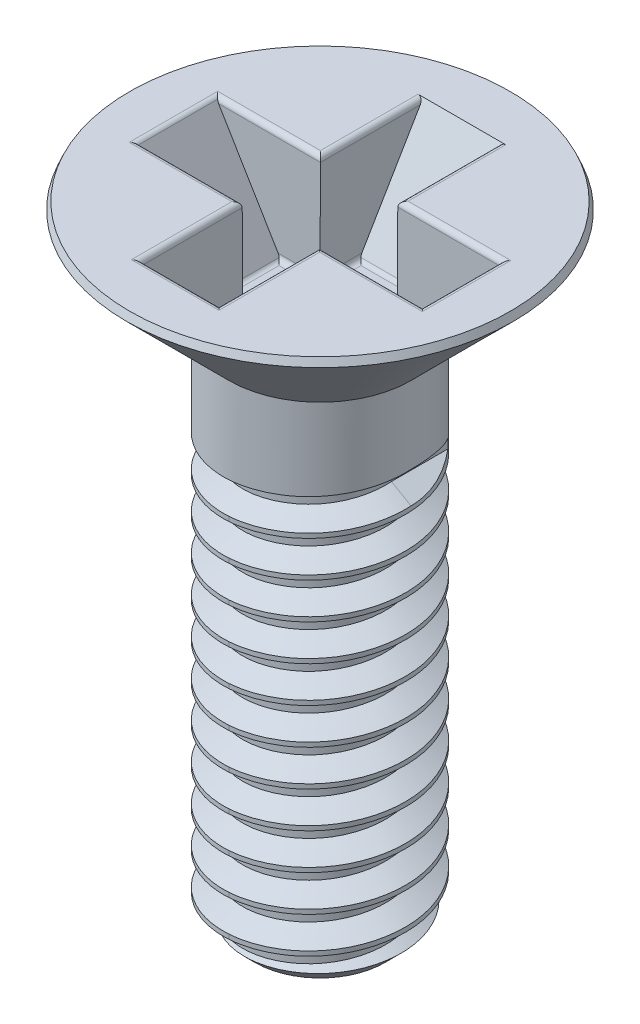
SolidWorks part; units mm, degrees
ref_plane "Alzado" through (0, 0, 0) normal (0, 0, 1) x (1, 0, 0)
ref_plane "Planta" through (0, 0, 0) normal (0, 1, 0) x (1, 0, 0)
ref_plane "Vista lateral" through (0, 0, 0) normal (1, 0, 0) x (0, 0, -1)
sketch "Croquis1" plane through (0, 0, 0) normal (0, 0, 1) x (1, 0, 0)
  line L0 (0, 0) -> (0, 5.3729) construction
  line L1 (0, 5.3729) -> (0, -5.1766) construction
  line L2 (0, 2.6864) -> (-3.6823, 2.6864)
  line L3 (-3.7409, 2.545) -> (-1.761, 0.5651)
  line L4 (-1.761, -8.9349) -> (-1.761, 0.5651)
  line L5 (-1.261, -9.4349) -> (0, -9.4349)
  line L6 (0, -9.4349) -> (0, 0.3991)
  line L9 (-1.261, -9.4349) -> (-1.761, -8.9349)
  line L10 (-3.6823, 2.6864) -> (-3.7409, 2.545)
  line L11 (0, 2.6864) -> (0, 0.3991)
  point P5 (-3.8823, 2.6864)
  point P7 (-1.761, -9.4349)
  dimension "D1" = 3
  dimension "D2" = 10
  dimension "D3" = 3.8823
  dimension "D4" = 45
  dimension "D5" = 1.761
revolve "Revolución1" add sketch "Croquis1" angle 360 about L11
ref_plane "Plano1" through (0, 0.5651, 0) normal (0, -1, 0) x (-1, 0, 0)
sketch "Croquis2" plane through (0, 0.5651, 0) normal (0, -1, 0) x (-1, 0, 0)
  line L0 (-0.75, 0.75) -> (-1.5, 0.75)
  line L1 (1.5, -0.75) -> (0.75, -0.75)
  line L2 (1.5, -0.75) -> (1.5, 0.75)
  line L3 (1.5, 0.75) -> (0.75, 0.75)
  line L4 (-1.5, -0.75) -> (-1.5, 0.75)
  line L5 (1.5, -0.75) -> (-1.5, 0.75) construction
  line L6 (1.5, 0.75) -> (-1.5, -0.75) construction
  line L7 (0.75, -1.5) -> (-0.75, -1.5)
  line L8 (0.75, -1.5) -> (0.75, -0.75)
  line L9 (0.75, 1.5) -> (-0.75, 1.5)
  line L10 (-0.75, -1.5) -> (-0.75, -0.75)
  line L11 (0.75, -1.5) -> (-0.75, 1.5) construction
  line L12 (0.75, 1.5) -> (-0.75, -1.5) construction
  line L13 (-0.75, 0.75) -> (-0.75, 1.5)
  line L14 (-0.75, -0.75) -> (-1.5, -0.75)
  line L15 (0.75, 0.75) -> (0.75, 1.5)
  point P0 (0, 0)
  point P6 (0, 0)
ref_plane "Plano3" through (0, 2.6864, 0) normal (0, 1, 0) x (1, 0, 0)
sketch "Croquis4" plane through (0, 2.6864, 0) normal (0, 1, 0) x (1, 0, 0)
  line L0 (0.7477, 0.7569) -> (0.7477, 2.7456)
  line L1 (-2.7792, -0.7569) -> (-0.7477, -0.7569)
  line L2 (-2.7792, -0.7569) -> (-2.7792, 0.7569)
  line L3 (-2.7792, 0.7569) -> (-0.7477, 0.7569)
  line L4 (2.7792, -0.7569) -> (2.7792, 0.7569)
  line L5 (-2.7792, -0.7569) -> (2.7792, 0.7569) construction
  line L6 (-2.7792, 0.7569) -> (2.7792, -0.7569) construction
  line L7 (-0.7477, -2.7456) -> (0.7477, -2.7456)
  line L8 (-0.7477, -2.7456) -> (-0.7477, -0.7569)
  line L9 (-0.7477, 2.7456) -> (0.7477, 2.7456)
  line L10 (0.7477, -2.7456) -> (0.7477, -0.7569)
  line L11 (-0.7477, -2.7456) -> (0.7477, 2.7456) construction
  line L12 (-0.7477, 2.7456) -> (0.7477, -2.7456) construction
  line L13 (0.7477, 0.7569) -> (2.7792, 0.7569)
  line L14 (-0.7477, 0.7569) -> (-0.7477, 2.7456)
  line L15 (0.7477, -0.7569) -> (2.7792, -0.7569)
  point P0 (0, 0)
  point P6 (0, 0)
loft "Cortar-Recubrir2" cut profiles "Croquis4", "Croquis2" connector at (-0.7477, 2.6864, 2.7456) connector at (-0.75, 0.5651, 1.5)
fillet "Redondeo1" radius 0.1 23 edges
thread "Rosca1" pitch 0.7 method cut profile "Perfil de rosca1" start angle 0, offset 1, length 0, pitch 0.7, diameter 3.522
ref_plane "Plano4" through (1.761, -9.9349, 0) normal (0, 0, 1) x (1, 0, 0)
sketch "Perfil de rosca1" plane through (1.761, -9.9349, 0) normal (0, 0, 1) x (1, 0, 0)
  line L0 (0, 0) -> (0, 0.7) construction
  line L11 (0, 0) -> (0, 0.6125)
  line L12 (0, 0.6125) -> (-0.3789, 0.3937)
  line L13 (-0.3789, 0.3937) -> (-0.3789, 0.2187)
  line L15 (-0.3789, 0.2187) -> (0, 0)
  line L17 (-0.3789, 0.3062) -> (0, 0.3062) construction
  point P2 (0, 0)
  dimension "Pitch" = 0.7
  dimension "Profile_Angle" = 60
  dimension "Profile_Land" = 0.175
  dimension "Profile_Height" = 0.3789
sketch "Croquis8" plane through (0, 0, 0) normal (0, 0, 1) x (1, 0, 0)
  line L0 (1.761, -1.5349) -> (1.761, -0.9224)
  line L1 (1.761, -0.9224) -> (1.3821, -1.1411)
  line L2 (1.3821, -1.1411) -> (1.3821, -1.3161)
  line L3 (1.3821, -1.3161) -> (1.761, -1.5349)
extrude "Cortar-Extruir1" cut sketch "Croquis8" against normal blind 10
